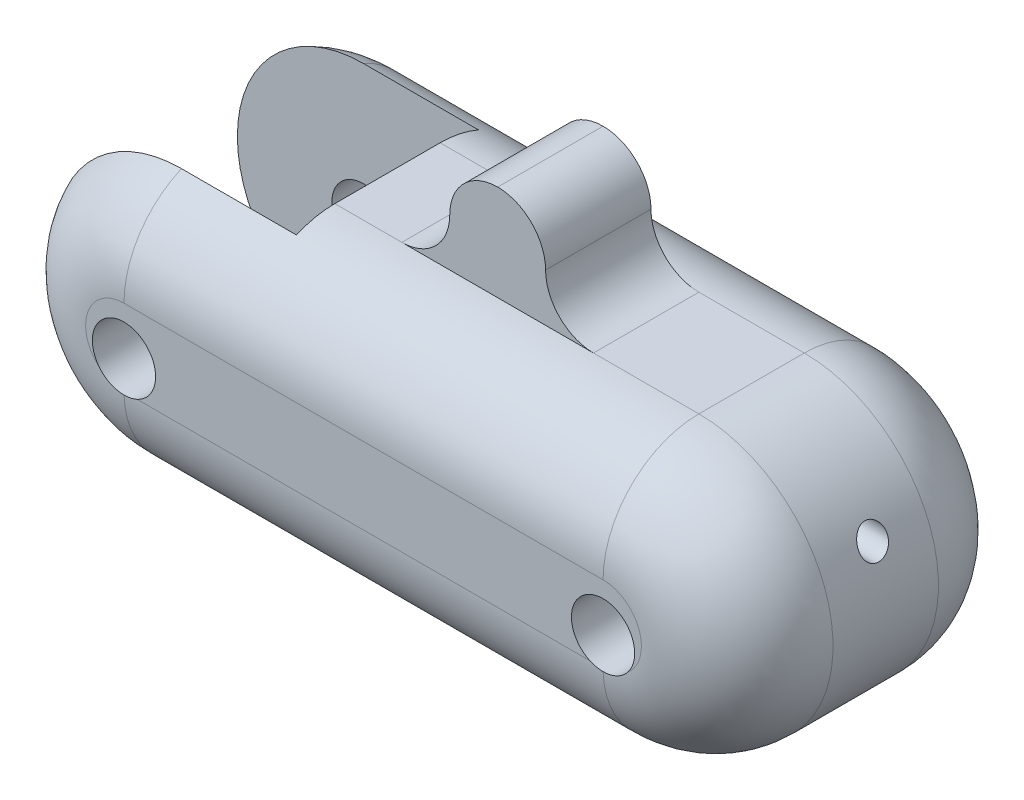
SolidWorks part; units mm, degrees
ref_plane "Front Plane" through (0, 0, 0) normal (0, 0, 1) x (1, 0, 0)
ref_plane "Top Plane" through (0, 0, 0) normal (0, 1, 0) x (1, 0, 0)
ref_plane "Right Plane" through (0, 0, 0) normal (1, 0, 0) x (0, 0, -1)
sketch "Sketch2" plane through (0, 0, 0) normal (0, 0, 1) x (1, 0, 0)
  line L0 (-12.5, 0) -> (12.5, 0)
  line L1 (-12.5, -14) -> (12.5, -14)
  arc A0 (-12.5, 0) -> (-12.5, -14) centre (-12.5, -7) ccw
  arc A1 (12.5, 0) -> (12.5, -14) centre (12.5, -7) cw
  point P4 (0, 0)
  dimension "D5" = 7
  dimension "D1" = 25
  dimension "D6" = 25
extrude "Boss-Extrude1" add sketch "Sketch2" along normal blind 15.5
fillet "Fillet1" radius 5 8 edges at (19.5, -7, 0) (0, -14, 0) (-19.5, -7, 0) (19.5, -7, 15.5) (0, -14, 15.5) (-19.5, -7, 15.5) (0, 0, 0) (0, 0, 15.5)
sketch "Sketch3" plane through (0, 0, 15.5) normal (0, 0, 1) x (1, 0, 0)
  circle A0 centre (-12.5, -7.5) radius 1.65
  circle A1 centre (12.5, -7.5) radius 1.65
  dimension "D1" = 3.3
ref_plane "Plane1" through (5.5, 0, 0) normal (-1, 0, 0) x (0, 0, 1)
ref_plane "Plane3" through (0, -25, 0) normal (0, -1, 0) x (-1, 0, 0)
sketch "Sketch5" plane through (0, -25, 0) normal (0, -1, 0) x (-1, 0, 0)
  line L1 (6.5, -3) -> (19.5, -3)
  line L2 (6.5, -3) -> (6.5, -12.5)
  line L3 (6.5, -12.5) -> (19.5, -12.5)
  line L4 (19.5, -3) -> (19.5, -12.5)
  line L9 (-12.5, 0) -> (12.5, 0) construction
  line L10 (12.5, -15.5) -> (-12.5, -15.5) construction
  line L11 (19.5, -10.5) -> (19.5, -5) construction
  dimension "D1" = 3
  dimension "D2" = 3
  dimension "D3" = 13
extrude "Cut-Extrude3" cut sketch "Sketch5" against normal through all
sketch "Sketch6" plane through (0, 0, 0) normal (0, 1, 0) x (1, 0, 0)
  line L1 (-0.5, -5) -> (4.5, -5)
  line L2 (-0.5, -5) -> (-0.5, -10.5)
  line L3 (-0.5, -10.5) -> (4.5, -10.5)
  line L4 (4.5, -5) -> (4.5, -10.5)
  line L5 (12.5, -10.5) -> (12.5, -15.5) construction
  line L6 (12.5, -5) -> (-6.5, -5) construction
  line L8 (-6.5, -10.5) -> (12.5, -10.5) construction
  dimension "D1" = 5
  dimension "D3" = 8
extrude "Boss-Extrude2" add sketch "Sketch6" along normal blind 5
fillet "Fillet2" radius 2.5 2 edges at (4.5, 5, 7.75) (-0.5, 5, 7.75)
fillet "Fillet3" radius 2.5 2 edges at (-0.5, 0, 7.75) (4.5, 0, 7.75)
extrude "Cut-Extrude4" cut sketch "Sketch3" against normal through all
ref_plane "Plane4" through (19.5, 0, 0) normal (1, 0, 0) x (0, 0, -1)
sketch "Sketch8" plane through (19.5, 0, 0) normal (1, 0, 0) x (0, 0, -1)
  line L0 (-10.5, -14) -> (-5, -14) construction
  circle A0 centre (-7.75, -4) radius 0.75
  point P6 (-7.75, -14)
  dimension "D1" = 1.5
  dimension "D2" = 4
extrude "Cut-Extrude7" cut sketch "Sketch8" against normal through all
sketch "Sketch9" plane through (-6.5, 0, 0) normal (-1, 0, 0) x (0, 0, 1)
  line L1 (10.5, -14) -> (5, -14) construction
  circle A0 centre (7.75, -10) radius 0.75
  dimension "D1" = 1.5
  dimension "D2" = 4
sketch "Sketch10" plane through (0, -14, 0) normal (0, -1, 0) x (1, 0, 0)
  line L0 (12.5, 10.5) -> (12.5, 5) construction
  line L2 (12.5, 15.4977) -> (12.5, 10.5) construction
  circle A0 centre (9.5, 7.75) radius 0.75
  point P5 (12.5, 7.75)
  point P10 (12.5, 12.9989)
  dimension "D1" = 1.5
  dimension "D2" = 3
sketch "Sketch11" plane through (0, 0, 15.5) normal (0, 0, 1) x (1, 0, 0)
  line L0 (-6.5, -10) -> (3.573, -14) construction
  line L1 (-6.5, -9.25) -> (-6.5, -10.75) construction
extrude "Cut-Extrude9" cut sketch "Sketch9" along direction (0.9294, -0.3691, 0) on the side against the normal up to vertex (16 mm away) contours A0 up to point (9.5, -14, 7.75)
